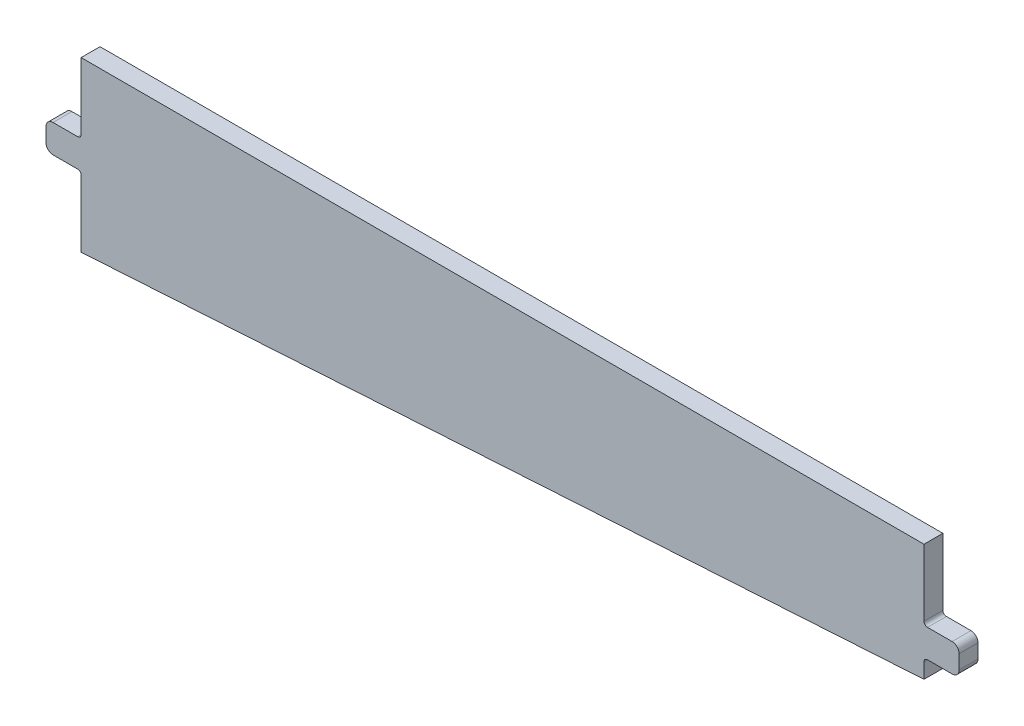
SolidWorks part; units mm, degrees
ref_plane "Front Plane" through (0, 0, 0) normal (0, 0, 1) x (1, 0, 0)
ref_plane "Top Plane" through (0, 0, 0) normal (0, 1, 0) x (1, 0, 0)
ref_plane "Right Plane" through (0, 0, 0) normal (1, 0, 0) x (0, 0, -1)
sketch "Sketch1" plane through (0, 0, 0) normal (0, 0, 1) x (1, 0, 0)
  line L1 (190.5, 38.1) -> (-190.5, 38.1)
  line L2 (190.5, 38.1) -> (190.5, -38.1)
  line L3 (190.5, -38.1) -> (-190.5, -38.1)
  line L4 (-190.5, 38.1) -> (-190.5, -38.1)
  line L5 (190.5, 38.1) -> (-190.5, -38.1) construction
  line L6 (190.5, -38.1) -> (-190.5, 38.1) construction
  point P0 (0, 0)
  point P6 (0, 0)
  point P8 (190.5, -16.2995)
  dimension "D1" = 381
  dimension "D2" = 76.2
extrude "Boss-Extrude1" add sketch "Sketch1" along normal mid plane 8.5342
sketch "Sketch3" plane through (0, 0, 4.2671) normal (0, 0, 1) x (1, 0, 0)
  line L1 (-190.5, 38.1) -> (-190.5, -38.1) construction
  line L2 (-190.5, 6.35) -> (-190.5, -6.35)
  line L3 (-190.5, 6.35) -> (-206.375, 6.35)
  line L4 (-206.375, 6.35) -> (-206.375, -6.35)
  line L5 (-206.375, -6.35) -> (-190.5, -6.35)
  point P0 (-190.5, 0)
  point P8 (-190.5, 0)
  dimension "D1" = 12.7
  dimension "D2" = 15.875
extrude "Boss-Extrude2" add sketch "Sketch3" against normal up to surface (8.5342 mm away) contours L5 L2 L3 L4 up to face at (0, 0, -4.2671)
fillet "Fillet1" radius 3.175 2 edges at (-206.375, -6.35, 0) (-206.375, 6.35, 0)
mirror "Mirror1" about plane through (0, 0, 0) normal (1, 0, 0) of "Fillet1", "Boss-Extrude2"
fillet "Fillet2" radius 1.5875 4 edges at (-190.5, -6.35, 0) (-190.5, 6.35, 0) (190.5, -6.35, 0) (190.5, 6.35, 0)
sketch "Sketch5" plane through (0, 0, 4.2671) normal (0, 0, 1) x (1, 0, 0)
  line L0 (-190.5, -38.1) -> (190.5, -14.797)
  line L1 (190.5, -38.1) -> (190.5, -7.9375) construction
  line L2 (190.5, -14.797) -> (190.5, -38.1)
  line L3 (190.5, -38.1) -> (-190.5, -38.1)
  dimension "D1" = 3.5
extrude "Cut-Extrude1" cut sketch "Sketch5" against normal through all
